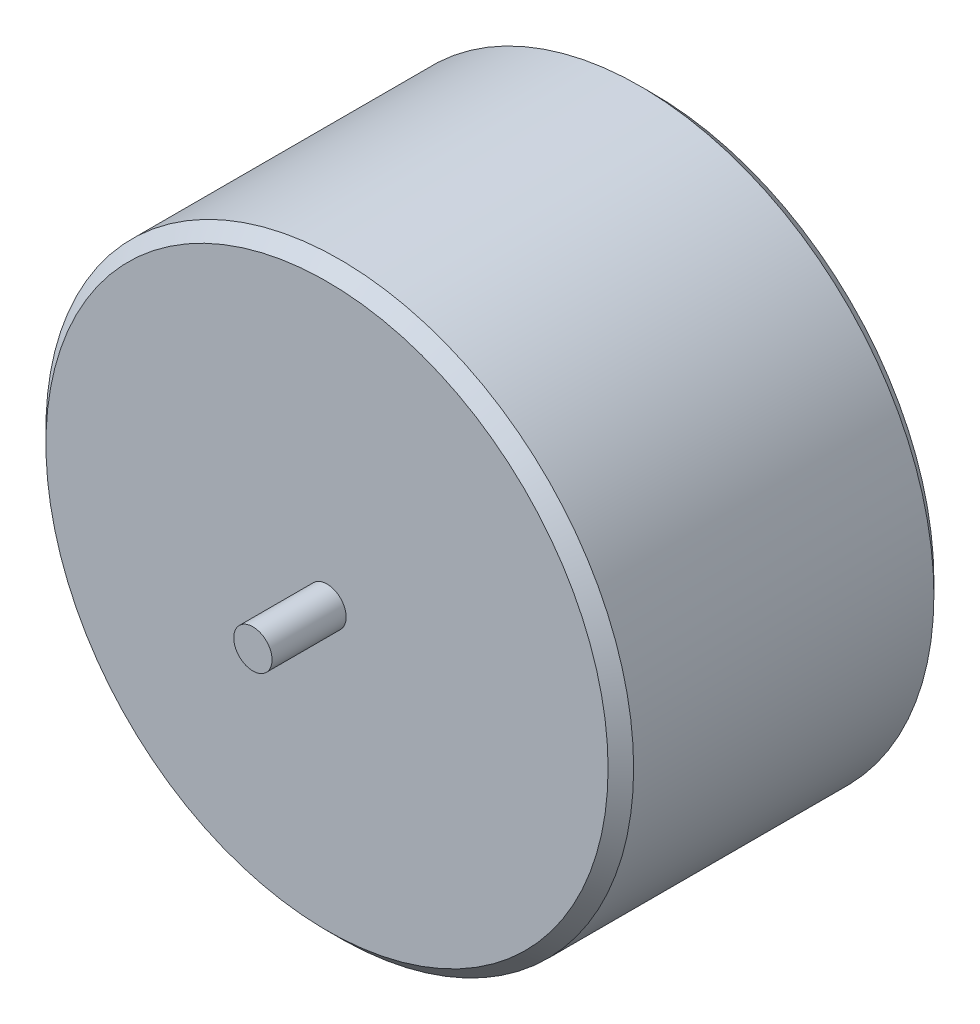
SolidWorks part; units mm, degrees
ref_plane "Plan de face" through (0, 0, 0) normal (0, 0, 1) x (1, 0, 0)
ref_plane "Plan de dessus" through (0, 0, 0) normal (0, 1, 0) x (1, 0, 0)
ref_plane "Plan de droite" through (0, 0, 0) normal (1, 0, 0) x (0, 0, -1)
sketch "Sketch1" plane through (0, 0, 0) normal (0, 0, 1) x (1, 0, 0)
  circle A0 centre (0, 0) radius 23
  dimension "D1" = 46
extrude "Boss-Extrude1" add sketch "Sketch1" along normal blind 25.5
sketch "Sketch3" plane through (0, 0, 25.5) normal (0, 0, 1) x (1, 0, 0)
  circle A0 centre (0, 0) radius 1.5
  dimension "D1" = 3
extrude "Boss-Extrude4" add sketch "Sketch3" along normal blind 5.8
chamfer "Chamfer1" distance 1 angle 45 2 edges at (23, 0, 0) (23, 0, 25.5)
